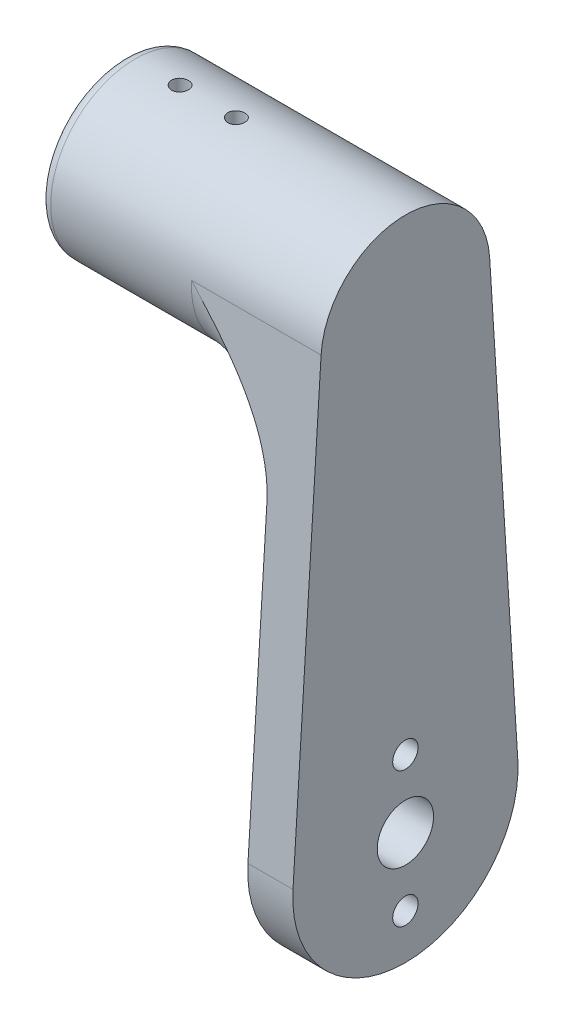
SolidWorks part; units mm, degrees
material "PETG"
ref_plane "Alzado" through (0, 0, 0) normal (0, 0, 1) x (1, 0, 0)
ref_plane "Planta" through (0, 0, 0) normal (0, 1, 0) x (1, 0, 0)
ref_plane "Vista lateral" through (0, 0, 0) normal (1, 0, 0) x (0, 0, -1)
sketch "Croquis1" plane through (0, 0, 0) normal (1, 0, 0) x (0, 0, -1)
  circle A0 centre (0, 0) radius 15
  circle A2 centre (0, 0) radius 9.55
  dimension "D1" = 19.1
  dimension "D2" = 30
extrude "Saliente-Extruir1" add sketch "Croquis1" along normal blind 40
sketch "Croquis3" plane through (0, 0, 0) normal (0, 1, 0) x (1, 0, 0)
  line L0 (40, -15) -> (40, 15) construction
  circle A0 centre (10, 0) radius 1.5
  circle A1 centre (20, 0) radius 1.5
  dimension "D3" = 3
  dimension "D4" = 3
  dimension "D1" = 20
  dimension "D2" = 10
extrude "Cortar-Extruir2" cut sketch "Croquis3" against normal through all and the other way through all
sketch "Croquis4" plane through (40, 0, 0) normal (1, 0, 0) x (0, 0, -1)
  circle A0 centre (0, 0) radius 15 construction
  circle A1 centre (0, 0) radius 15
extrude "Saliente-Extruir2" add sketch "Croquis4" along normal blind 2
sketch "Croquis5" plane through (42, 0, 0) normal (1, 0, 0) x (0, 0, -1)
  line L0 (-14.9707, 0.9375) -> (-19.9609, -78.75)
  line L1 (14.9707, 0.9375) -> (19.9609, -78.75)
  arc A0 (-19.9609, -78.75) -> (19.9609, -78.75) centre (0, -80) ccw
  circle A3 centre (0, 0) radius 15 construction
  arc A4 (14.9707, 0.9375) -> (-14.9707, 0.9375) centre (0, 0) ccw
  arc A5 (-14.9707, 0.9375) -> (14.9707, 0.9375) centre (0, 0) ccw construction
  arc A6 (19.9609, -78.75) -> (-19.9609, -78.75) centre (0, -80) ccw construction
  dimension "D1" = 40
  dimension "D2" = 80
extrude "Saliente-Extruir3" add sketch "Croquis5" along normal blind 8
sketch "Croquis6" plane through (50, 0, 0) normal (1, 0, 0) x (0, 0, -1)
  circle A0 centre (0, -80) radius 5
  dimension "D1" = 10
extrude "Cortar-Extruir3" cut sketch "Croquis6" against normal through all
fillet "Redondeo1" radius 2 1 edges at (0, 0, -15)
sketch "Croquis7" plane through (50, 0, 0) normal (1, 0, 0) x (0, 0, -1)
  circle A0 centre (0, -92) radius 2.25
  circle A1 centre (0, -68) radius 2.25
  circle A2 centre (0, -80) radius 5 construction
  circle A3 centre (0, -80) radius 5 construction
  dimension "D1" = 4.5
  dimension "D2" = 4.5
  dimension "D4" = 12
  dimension "D3" = 24
extrude "Cortar-Extruir4" cut sketch "Croquis7" against normal blind 10
fillet "Redondeo2" radius 15 1 edges at (42, -15, 0)
